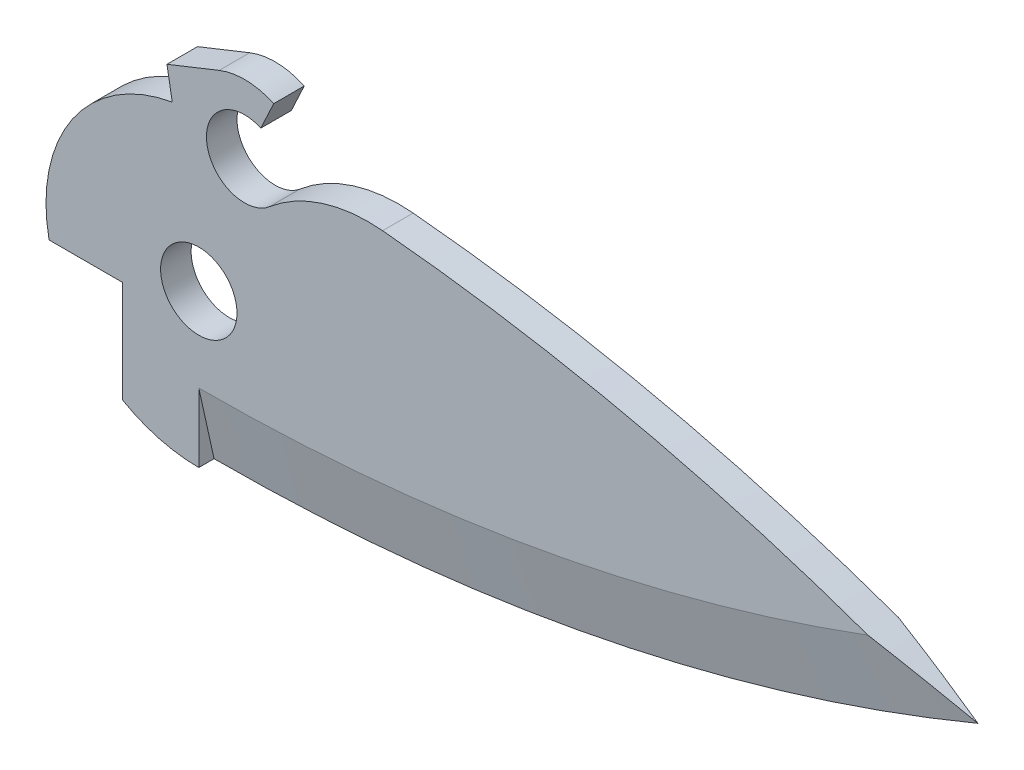
SolidWorks part; units mm, degrees
material "1.2316 (X36CrMo17)"
ref_plane "Přední rovina" through (0, 0, 0) normal (0, 0, 1) x (1, 0, 0)
ref_plane "Horní rovina" through (0, 0, 0) normal (0, 1, 0) x (1, 0, 0)
ref_plane "Pravá rovina" through (0, 0, 0) normal (1, 0, 0) x (0, 0, -1)
sketch "Skica1" plane through (0, 0, 0) normal (0, 0, 1) x (1, 0, 0)
  line L0 (0, 0) -> (28.9614, 0) construction
  line L1 (1.3336, 13.1801) -> (-2.0838, 11.8177)
  line L2 (-2.0838, 11.8177) -> (-1.7365, 9.8481)
  line L3 (0, 10) -> (0, -10) construction
  line L4 (3, 9) -> (3, 16.5233) construction
  line L5 (4.0565, 11.2658) -> (4.9018, 13.0784)
  line L7 (0, 0) -> (58.3677, 0) construction
  line L8 (0, 0) -> (-0.0542, 0.0512) construction
  circle A0 centre (0, 0) radius 2.5
  arc A1 (-1.7365, 9.8481) -> (-10, 0) centre (0, 0) ccw
  arc A2 (12.0319, 9.442) -> (50, 0) centre (0, -120) cw
  arc A3 (0, -10) -> (50, 0) centre (0, 120) ccw
  arc A4 (4.0565, 11.2658) -> (4.6213, 7.097) centre (3, 9) ccw
  arc A5 (12.0319, 9.442) -> (4.6213, 7.097) centre (11.1064, -0.5151) ccw
  arc A6 (4.9018, 13.0784) -> (1.3336, 13.1801) centre (3, 9) ccw
  arc A9 (-10, 0) -> (0, -10) centre (0, 0) ccw
  dimension "D1" = 10
  dimension "D2" = 5
  dimension "D3" = 60
  dimension "D5" = 2.5
  dimension "D6" = 2
  dimension "D8" = 10
  dimension "D11" = 10
  dimension "D12" = 0
  dimension "D4" = 3
  dimension "D7" = 25
  dimension "D9" = 2
  dimension "D10" = 9
extrude "Přidat vysunutím1" add sketch "Skica1" along normal mid plane 2
sketch "Skica2" plane through (0, 0, 0) normal (1, 0, 0) x (0, 0, -1)
  line L0 (0, -10) -> (1, -5.4893)
  line L1 (-1, -10) -> (1, -10) construction
  line L2 (1, -10) -> (1, 9.8481) construction
  line L3 (0, -10) -> (0, -2.6677) construction
  line L4 (0, -10) -> (-1, -5.4893)
  line L5 (-1, -5.4893) -> (-1, -10)
  line L6 (-1, -10) -> (0, -10)
  line L7 (1, -5.4893) -> (1, -10)
  line L8 (1, -10) -> (0, -10)
  line L9 (0, -10) -> (0.0115, -9.9693)
  dimension "D1" = 25
sketch "Skica3" plane through (0, 0, 0) normal (0, 0, 1) x (1, 0, 0)
  arc A0 (0, -10) -> (50, 0) centre (0, 120) ccw construction
  arc A1 (0, -10) -> (50, 0) centre (0, 120) ccw
sweep "Odebrat tažením po křivce1" cut profiles "Skica2" path "Skica3"
mirror "Zrcadlit1" about plane through (0, 0, 0) normal (0, 0, 1) of "Odebrat tažením po křivce1"
sketch "Skica4" plane through (0, 0, 0) normal (0, 0, 1) x (1, 0, 0)
  line L0 (-5, -2) -> (-5, -12.5089)
  line L1 (-5, -2) -> (-13.094, -2)
  dimension "D2" = 2
  dimension "D3" = 90
  dimension "D1" = 5
extrude "Odebrat vysunutím1" cut sketch "Skica4" against normal through all and the other way through all
